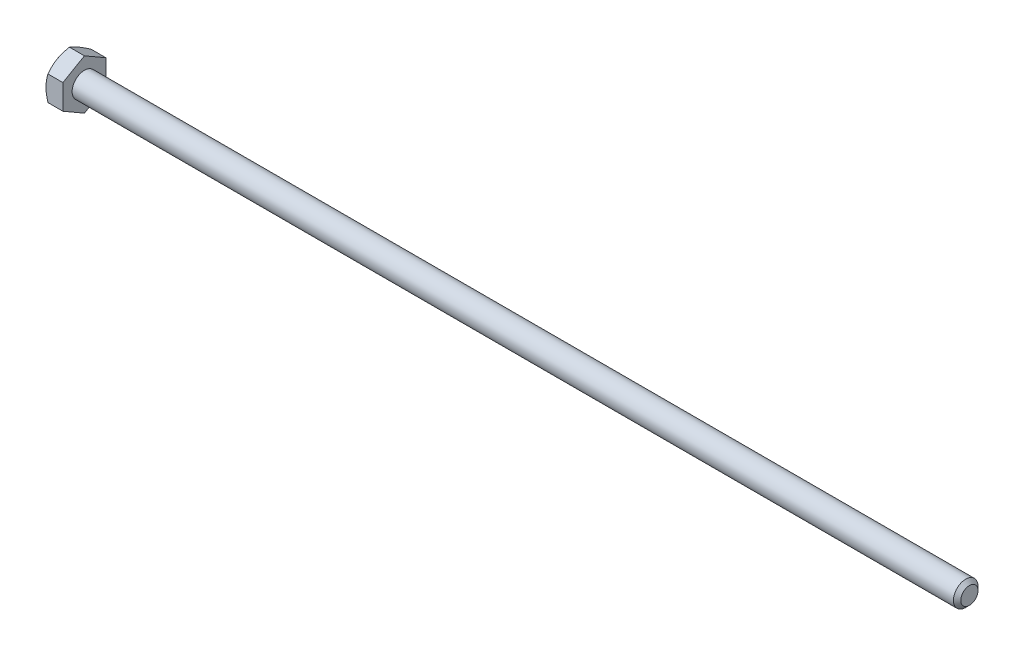
SolidWorks part; units mm, degrees
material "Alloy Steel"
ref_plane "Front Plane" through (0, 0, 0) normal (0, 0, 1) x (1, 0, 0)
ref_plane "Top Plane" through (0, 0, 0) normal (0, 1, 0) x (1, 0, 0)
ref_plane "Right Plane" through (0, 0, 0) normal (1, 0, 0) x (0, 0, -1)
sketch "Sketch1" plane through (0, 0, 0) normal (0, 0, 1) x (1, 0, 0)
  line L0 (-116.4828, 0) -> (116.4828, 0) construction
  line L1 (116.4828, 3.175) -> (116.4828, -3.175) construction
  line L2 (-112.1172, 5.5562) -> (-112.1172, -5.5562) construction
  line L3 (-116.4828, 5.5562) -> (-116.4828, -5.5562) construction
  point P9 (-112.1172, 0)
  point P10 (112.0378, -3.175)
  point P11 (91.0828, 0)
  dimension "D1" = 4.445
ref_plane "Plane2" through (116.4828, 0, 0) normal (1, 0, 0) x (0, 0, -1)
sketch "Sketch5" plane through (116.4828, 0, 0) normal (1, 0, 0) x (0, 0, -1)
  circle A0 centre (0, 0) radius 3.175
extrude "Boss-Extrude3" add sketch "Sketch5" against normal up to vertex (228.6 mm away) up to point (-112.1172, 0, 0)
sketch "Sketch9" [suppressed] plane through (116.4828, 0, 0) normal (1, 0, 0) x (0, 0, -1)
  circle A1 centre (0, 0) radius 3.175
  circle A2 centre (0, 0) radius 3.175
  dimension "D1" = 0
chamfer "Chamfer1" distance 0.9525 angle 45 1 edges at (116.4828, 0, -3.175)
sketch "Sketch11" plane through (0, 0, 0) normal (0, 0, 1) x (1, 0, 0)
  line L0 (-112.1172, 3.175) -> (-112.1172, 0)
  line L1 (-112.1172, 0) -> (94.2578, 0)
  line L3 (94.2578, 0) -> (91.0828, 3.175)
  line L4 (-112.1172, 3.175) -> (91.0828, 3.175)
  dimension "D1" = 45
  dimension "MIn Thread" = 25.4
revolve "Revolve1" add sketch "Sketch11" angle 360 about L1
sketch "Sketch6" plane through (-112.1172, 0, 0) normal (-1, 0, 0) x (0, 0, 1)
  line L0 (0, 5.5562) -> (0, -5.5562) construction
  line L1 (5.5563, 3.2079) -> (0, 6.4158)
  line L2 (0, 6.4158) -> (-5.5562, 3.2079)
  line L3 (-5.5562, 3.2079) -> (-5.5562, -3.2079)
  line L4 (-5.5562, -3.2079) -> (0, -6.4158)
  line L5 (0, -6.4158) -> (5.5563, -3.2079)
  line L6 (5.5563, -3.2079) -> (5.5563, 3.2079)
  circle A0 centre (0, 0) radius 5.5562 construction
extrude "Boss-Extrude4" add sketch "Sketch6" along normal up to vertex (4.3656 mm away) up to point (-116.4828, -5.5562, 0)
sketch "Sketch7" plane through (-116.4828, 0, 0) normal (-1, 0, 0) x (0, 0, 1)
  circle A0 centre (0, 0) radius 5.5562 construction
  circle A1 centre (0, 0) radius 5.5562
sketch "Sketch8" plane through (-116.4828, 0, 0) normal (-1, 0, 0) x (0, 0, 1)
  circle A0 centre (0, 0) radius 5.5562 construction
  circle A1 centre (0, 0) radius 5.5562
extrude "Cut-Extrude3" cut sketch "Sketch8" against normal through all draft 60 flip side to cut
sketch "Sketch12" plane through (-116.4828, 0, 0) normal (-1, 0, 0) x (0, 0, 1)
  line L0 (0, 4.2783) -> (0, 2.3892) construction
  line L1 (0.1667, 4.2783) -> (0.1667, 2.3892)
  line L2 (-0.1667, 4.2783) -> (-0.1667, 2.3892)
  line L3 (0, 3.175) -> (0, -3.175) construction
  arc A0 (0.1667, 4.2783) -> (-0.1667, 4.2783) centre (0, 4.2783) ccw
  arc A1 (-0.1667, 2.3892) -> (0.1667, 2.3892) centre (0, 2.3892) ccw
  circle A3 centre (0, 0) radius 2.2225 construction
  circle A4 centre (0, 0) radius 4.445 construction
  point P2 (0, 3.3337)
  dimension "D1" = 4.445
  dimension "D3" = 8.89
  dimension "D2" = 0.3334
extrude "Cut-Extrude4" cut sketch "Sketch12" against normal blind 0.254
pattern_circular "CirPattern1" count 6 over 360 about axis through (-112.1172, 0, 0) along (1, 0, 0) of "Cut-Extrude4"
ref_plane "Plane3" through (91.0828, 0, 0) normal (1, 0, 0) x (0, 0, -1)
ref_axis "Center Axis1" through (146.542, 0, 0) along (-1, 0, 0)
ref_plane "Contact Plane1" through (91.0828, 0, 0) normal (1, 0, 0) x (0, 0, -1)
ref_plane "Contact Plane2" through (-112.1172, 0, 0) normal (1, 0, 0) x (0, 0, -1)
split "Split1" [suppressed] bodies to split 117
curve "Helix/Spiral1" [suppressed] pitch 1.27 height 26.67 turns 21 parameters "Pitch"=1.27
sketch "Sketch10" [suppressed] plane through (0, 0, 0) normal (0, 0, 1) x (1, 0, 0)
  line L0 (116.4828, 3.175) -> (116.9591, 2.3501)
  line L1 (116.9591, 2.3501) -> (117.1178, 2.3501)
  line L2 (117.1178, 2.3501) -> (117.5941, 3.175)
  line L3 (116.4828, 3.175) -> (117.5941, 3.175)
  line L4 (117.0384, 3.175) -> (117.0384, 2.3501) construction
  line L5 (116.7209, 2.7626) -> (117.3559, 2.7626) construction
  dimension "D1" = 60
  dimension "D2" = 0.1588
  dimension "D3" = 0.635
sweep "Cut-Sweep1" [suppressed] cut profiles "Sketch10" path "Helix/Spiral1"
sketch "Sketch13" [suppressed] plane through (91.0828, 0, 0) normal (1, 0, 0) x (0, 0, -1)
  circle A1 centre (0, 0) radius 3.175
  circle A2 centre (0, 0) radius 3.175
  dimension "D1" = 0
extrude "Boss-Extrude5" [suppressed] add sketch "Sketch13" along normal through all draft 60
equation "\"D2@Sketch10\" = \"Pitch@Helix/Spiral1\"*.125"
equation "\"D3@Sketch10\" = \"Pitch@Helix/Spiral1\"*.5"
equation "\"D3@Helix/Spiral1\"=\"Thread Length@Sketch1\"+\"Pitch@Helix/Spiral1\""
equation "\"D1@Chamfer1\" = \"Pitch@Helix/Spiral1\"*.75"
equation "\"D1@Sketch12\" = \"Hex@Sketch1\"*.4"
equation "\"D3@Sketch12\" = \"Hex@Sketch1\"*.8"
equation "\"D2@Sketch12\" = \"Hex@Sketch1\"*.03"
equation "\"D1@Sketch1\" = \"Pitch@Helix/Spiral1\"*3.5"
